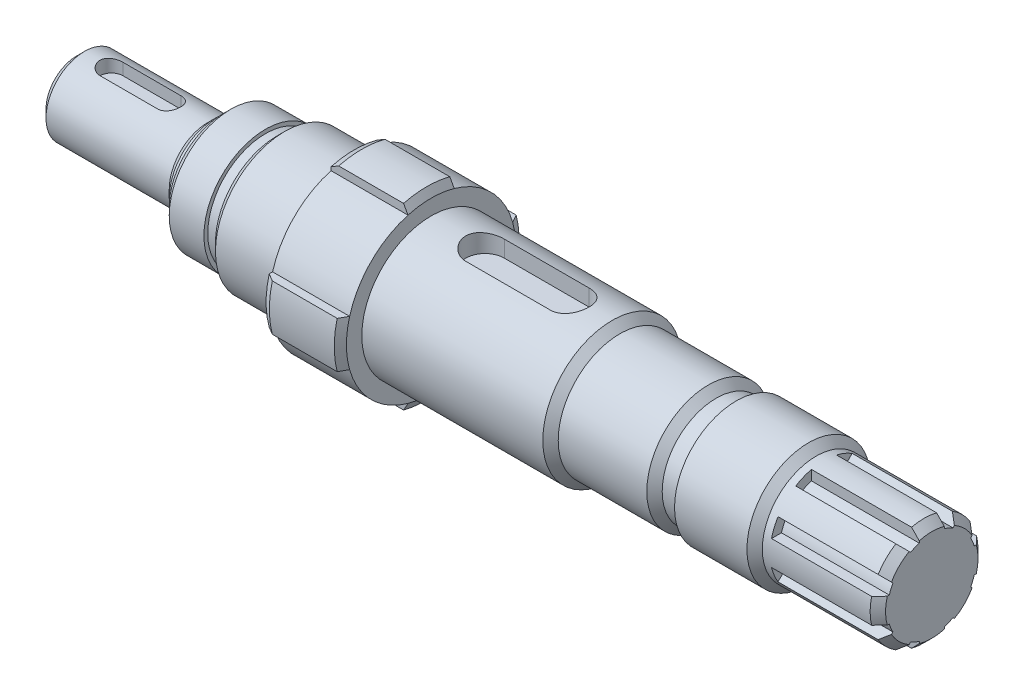
SolidWorks part; units mm, degrees
ref_plane "Front Plane" through (0, 0, 0) normal (0, 0, 1) x (1, 0, 0)
ref_plane "Top Plane" through (0, 0, 0) normal (0, 1, 0) x (1, 0, 0)
ref_plane "Right Plane" through (0, 0, 0) normal (1, 0, 0) x (0, 0, -1)
sketch "Croquis1" plane through (0, 0, 0) normal (0, 0, 1) x (1, 0, 0)
  line L0 (0, 0) -> (0, 10)
  line L1 (0, 10) -> (34, 10)
  line L2 (34, 10) -> (34, 12)
  line L3 (34, 12) -> (38, 12)
  line L4 (38, 12) -> (38, 16)
  line L5 (38, 16) -> (49, 16)
  line L6 (49, 16) -> (49, 15)
  line L7 (49, 15) -> (52, 15)
  line L8 (52, 15) -> (52, 18)
  line L9 (52, 18) -> (72, 18)
  line L10 (72, 18) -> (72, 24)
  line L11 (72, 24) -> (92, 24)
  line L12 (92, 24) -> (92, 18)
  line L13 (92, 18) -> (141, 18)
  line L14 (141, 18) -> (141, 16)
  line L15 (141, 16) -> (166, 16)
  line L16 (192, 16) -> (192, 14)
  line L17 (192, 14) -> (222, 14)
  line L18 (222, 14) -> (222, 0)
  line L19 (0, 0) -> (222, 0)
  line L20 (166, 16) -> (166, 14)
  line L21 (0, 0) -> (222, 0) construction
  line L23 (166, 14) -> (171.2009, 14)
  line L24 (171.2009, 14) -> (171.2009, 16)
  line L25 (171.2009, 16) -> (192, 16)
  point P19 (36, 12)
  dimension "D1" = 222
  dimension "D2" = 34
  dimension "D3" = 38
  dimension "D4" = 52
  dimension "D5" = 3
  dimension "D6" = 72
  dimension "D7" = 30
  dimension "D8" = 56
  dimension "D9" = 81
  dimension "D10" = 130
  dimension "D11" = 20
  dimension "D12" = 24
  dimension "D13" = 32
  dimension "D14" = 30
  dimension "D15" = 36
  dimension "D16" = 48
  dimension "D17" = 28
  dimension "D18" = 28
revolve "Revolución1" add sketch "Croquis1" angle 360 about L19
chamfer "Chaflán1" distance 2 angle 45 5 edges at (166, 0, 16) (192, 0, 16) (141, 0, 18) (34, 0, 12) (0, 0, 10)
chamfer "Chaflán2" distance 2 angle 45 2 edges at (52, 0, 18) (38, 0, 16)
chamfer "Chaflán3" distance 2 angle 30 2 edges at (92, 0, 24) (72, 0, 24) first distance on face at (92, 0, 24) first distance on face at (72, 0, 24)
chamfer "Chaflán4" distance 2 angle 45 1 edges at (222, 0, 14)
ref_plane "Plano1" through (0, 10, 0) normal (0, 1, 0) x (1, 0, 0)
sketch "Croquis3" plane through (0, 10, 0) normal (0, 1, 0) x (1, 0, 0)
  line L0 (0, 0) -> (34.3395, 0) construction
  line L1 (9, 0) -> (24, 0) construction
  line L2 (9, 3) -> (24, 3)
  line L3 (9, -3) -> (24, -3)
  arc A0 (9, 3) -> (9, -3) centre (9, 0) ccw
  arc A1 (24, -3) -> (24, 3) centre (24, 0) ccw
  point P5 (16.5, 0)
  dimension "D3" = 3
  dimension "D1" = 9
  dimension "D2" = 15
extrude "Cortar-Extruir1" cut sketch "Croquis3" against normal blind 3.5
ref_plane "Plano4" through (0, 18, 0) normal (0, 1, 0) x (1, 0, 0)
sketch "Croquis5" plane through (0, 18, 0) normal (0, 1, 0) x (1, 0, 0)
  line L0 (92, 0) -> (139, 0) construction
  line L1 (92, -18) -> (92, 18) construction
  line L2 (139, -18) -> (139, 18) construction
  line L3 (106, 0) -> (128, 0) construction
  line L4 (106, 5) -> (128, 5)
  line L5 (106, -5) -> (128, -5)
  arc A0 (106, 5) -> (106, -5) centre (106, 0) ccw
  arc A1 (128, -5) -> (128, 5) centre (128, 0) ccw
  point P8 (117, 0)
  dimension "D1" = 5
  dimension "D2" = 22
  dimension "D3" = 14
extrude "Cortar-Extruir2" cut sketch "Croquis5" against normal blind 5
sketch "Croquis7" plane through (92, 0, 0) normal (1, 0, 0) x (0, 0, -1)
  line L0 (0, 0) -> (0, 24) construction
  line L1 (-6, 25.5202) -> (-6, 20.1246)
  line L2 (6, 25.5202) -> (6, 20.1246)
  line L3 (25.5202, 6) -> (20.1246, 6)
  line L4 (25.5202, -6) -> (20.1246, -6)
  line L5 (6, -25.5202) -> (6, -20.1246)
  line L6 (-6, -25.5202) -> (-6, -20.1246)
  line L7 (-25.5202, -6) -> (-20.1246, -6)
  line L8 (-25.5202, 6) -> (-20.1246, 6)
  line L9 (0, 0) -> (24, 0) construction
  circle A0 centre (0, 0) radius 24
  circle A1 centre (0, 0) radius 22
  circle A2 centre (0, 0) radius 22
  circle A3 centre (0, 0) radius 24
  circle A4 centre (0, 0) radius 24
  circle A5 centre (0, 0) radius 21
  point P28 (0, 0)
  circle M8 centre (0, 0) radius 22
  dimension "D3" = 48
  dimension "D4" = 42
  dimension "D5" = 12
  dimension "D1" = 0
  dimension "D2" = 0
  dimension "D6" = 4
extrude "Cortar-Extruir3" cut sketch "Croquis7" against normal through all contours L3 A0 L2 M8 | L5 A0 L4 M8 | L7 A0 L6 M8 | L1 A0 L8 M8 region at (92, 22.202, 6.2438) region at (92, 16.7982, -16.7982) region at (92, -6.2438, 22.202) region at (92, -16.7982, -16.7982)
sketch "Croquis8" plane through (222, 0, 0) normal (1, 0, 0) x (0, 0, -1)
  line L0 (0, 0) -> (0, 11.5) construction
  line L1 (-3.25, 13.6175) -> (-3.25, 11.0312)
  line L2 (3.25, 13.6175) -> (3.25, 11.0312)
  line L3 (0, 0) -> (12, 0) construction
  line L4 (7.331, 11.9272) -> (5.5021, 10.0983)
  line L5 (11.9272, 7.331) -> (10.0983, 5.5021)
  line L6 (13.6175, 3.25) -> (11.0312, 3.25)
  line L7 (13.6175, -3.25) -> (11.0312, -3.25)
  line L8 (11.9272, -7.331) -> (10.0983, -5.5021)
  line L9 (7.331, -11.9272) -> (5.5021, -10.0983)
  line L10 (3.25, -13.6175) -> (3.25, -11.0312)
  line L11 (-3.25, -13.6175) -> (-3.25, -11.0312)
  line L12 (-7.331, -11.9272) -> (-5.5021, -10.0983)
  line L13 (-11.9272, -7.331) -> (-10.0983, -5.5021)
  line L14 (-13.6175, -3.25) -> (-11.0312, -3.25)
  line L15 (-13.6175, 3.25) -> (-11.0312, 3.25)
  line L16 (-11.9272, 7.331) -> (-10.0983, 5.5021)
  line L17 (-7.331, 11.9272) -> (-5.5021, 10.0983)
  arc A0 (-10.0983, 5.5021) -> (-11.0312, 3.25) centre (0, 0) ccw
  circle A1 centre (0, 0) radius 12 construction
  circle A2 centre (0, 0) radius 14
  arc A3 (-11.9272, 7.331) -> (-13.6175, 3.25) centre (0, 0) ccw
  arc A4 (-3.25, 11.0312) -> (-5.5021, 10.0983) centre (0, 0) ccw
  arc A5 (-3.25, 13.6175) -> (-7.331, 11.9272) centre (0, 0) ccw
  arc A6 (5.5021, 10.0983) -> (3.25, 11.0312) centre (0, 0) ccw
  arc A7 (7.331, 11.9272) -> (3.25, 13.6175) centre (0, 0) ccw
  arc A8 (11.0312, 3.25) -> (10.0983, 5.5021) centre (0, 0) ccw
  arc A9 (13.6175, 3.25) -> (11.9272, 7.331) centre (0, 0) ccw
  arc A10 (10.0983, -5.5021) -> (11.0312, -3.25) centre (0, 0) ccw
  arc A11 (11.9272, -7.331) -> (13.6175, -3.25) centre (0, 0) ccw
  arc A12 (3.25, -11.0312) -> (5.5021, -10.0983) centre (0, 0) ccw
  arc A13 (3.25, -13.6175) -> (7.331, -11.9272) centre (0, 0) ccw
  arc A14 (-5.5021, -10.0983) -> (-3.25, -11.0312) centre (0, 0) ccw
  arc A15 (-7.331, -11.9272) -> (-3.25, -13.6175) centre (0, 0) ccw
  arc A16 (-11.0312, -3.25) -> (-10.0983, -5.5021) centre (0, 0) ccw
  arc A17 (-13.6175, -3.25) -> (-11.9272, -7.331) centre (0, 0) ccw
  point P44 (0, 0)
  dimension "D1" = 23
  dimension "D2" = 0
  dimension "D3" = 6.5
  dimension "D4" = 8
extrude "Cortar-Extruir4" cut sketch "Croquis8" against normal blind 28
